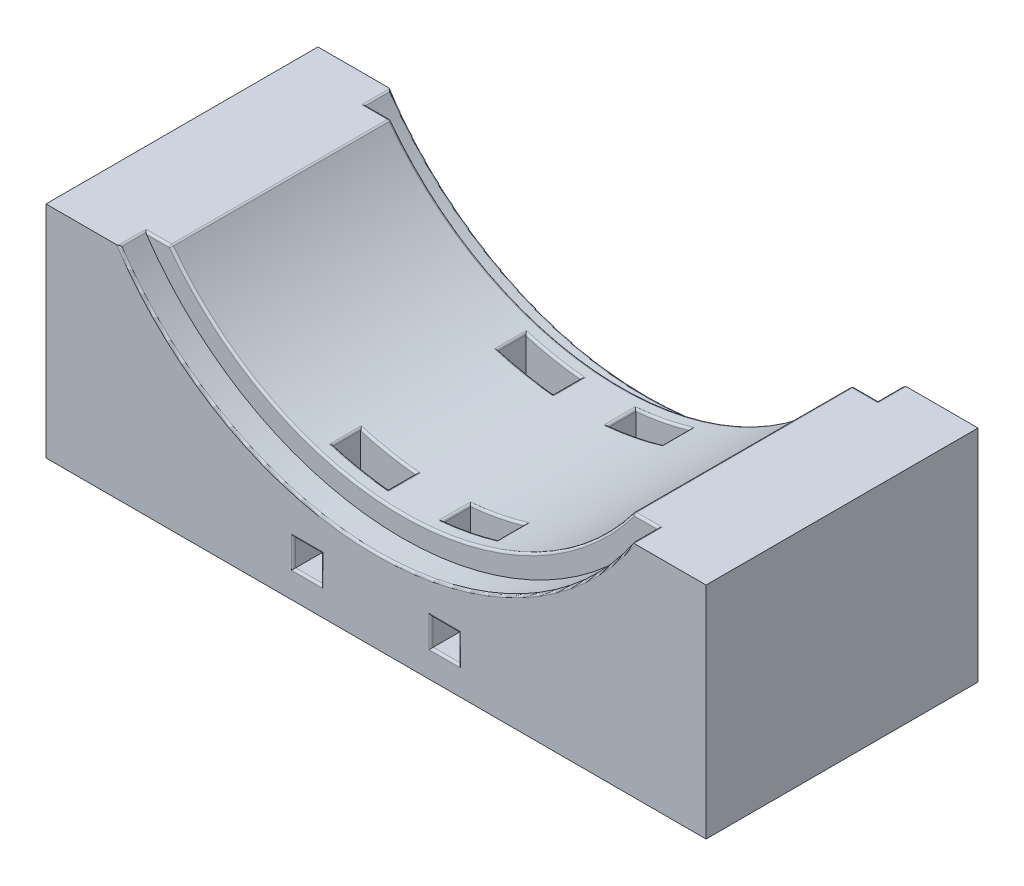
SolidWorks part; units mm, degrees
material "ABS"
ref_plane "Front Plane" through (0, 0, 0) normal (0, 0, 1) x (1, 0, 0)
ref_plane "Top Plane" through (0, 0, 0) normal (0, 1, 0) x (1, 0, 0)
ref_plane "Right Plane" through (0, 0, 0) normal (1, 0, 0) x (0, 0, -1)
sketch "Sketch1" plane through (0, 0, 0) normal (0, 0, 1) x (1, 0, 0)
  line L0 (0, 0) -> (-33941.0899, 0) construction
  line L1 (0, 0) -> (0, 33941.0899) construction
  line L3 (-76.2, 0) -> (76.2, 0)
  line L4 (-76.2, 0) -> (-76.2, 50.8)
  line L5 (-76.2, 50.8) -> (76.2, 50.8)
  line L6 (76.2, 0) -> (76.2, 50.8)
  circle A0 centre (0, 90.4875) radius 71.374
  dimension "D2" = 142.748
  dimension "D3" = 50.8
  dimension "D1" = 90.4875
  dimension "D4" = 152.4
extrude "Boss-Extrude1" add sketch "Sketch1" along normal blind 5.9944 contours A0 L5 L4 L3 L6 region at (0, 18.9439, 0)
sketch "Sketch2" plane through (0, 0, 5.9944) normal (0, 0, 1) x (1, 0, 0)
  line L0 (0, 0) -> (0, 50000) construction
  line L1 (0, 0) -> (-50000, 0) construction
  line L2 (-76.2, 0) -> (76.2, 0) construction
  line L4 (-76.2, 50.8) -> (76.2, 50.8)
  line L5 (-76.2, 50.8) -> (-76.2, 0)
  line L6 (-76.2, 0) -> (76.2, 0)
  line L7 (76.2, 50.8) -> (76.2, 0)
  circle A0 centre (0, 90.4875) radius 66.548
  point P7 (0, 0)
  arc M2 (59.3224, 50.8) -> (-59.3224, 50.8) centre (0, 90.4875) cw
  line M3 (-59.3224, 50.8) -> (-76.2, 50.8)
  line M4 (-76.2, 50.8) -> (-76.2, 0)
  line M5 (-76.2, 0) -> (76.2, 0)
  line M6 (76.2, 0) -> (76.2, 50.8)
  line M7 (76.2, 50.8) -> (59.3224, 50.8)
  dimension "D1" = 133.096
  dimension "D2" = 90.4875
extrude "Boss-Extrude2" add sketch "Sketch2" along normal blind 50.8 contours A0 L4 M2 | M7 M2 M3 M4 M5 M6 region at (0, 18.9439, 5.9944) region at (-56.3705, 49.572, 5.9944)
sketch "Sketch3" plane through (0, 0, 56.7944) normal (0, 0, 1) x (1, 0, 0)
  line L0 (0, 0) -> (0, 50000) construction
  line L1 (0, 0) -> (-47845.2173, 0) construction
  line L4 (-76.2, 50.8) -> (76.2, 50.8)
  line L5 (-76.2, 50.8) -> (-76.2, 0)
  line L6 (-76.2, 0) -> (76.2, 0)
  line L7 (76.2, 50.8) -> (76.2, 0)
  circle A0 centre (0, 90.4875) radius 71.374
  line M4 (-76.2, 50.8) -> (-76.2, 0)
  line M5 (-76.2, 0) -> (76.2, 0)
  line M6 (76.2, 0) -> (76.2, 50.8)
  line M7 (76.2, 50.8) -> (53.4185, 50.8)
  dimension "D1" = 142.748
  dimension "D2" = 90.4875
extrude "Boss-Extrude3" add sketch "Sketch3" along normal blind 5.9944 contours A0 L4 M4 M5 M6 M7 region at (0, 18.9439, 56.7944)
fillet "Fillet1" radius 0.508 14 edges at (0, 19.1135, 62.7888) (0, 23.9395, 56.7944) (0, 19.1135, 0) (0, 23.9395, 5.9944) (-53.4185, 50.8, 31.3944) (53.4185, 50.8, 31.3944)
ref_plane "Plane1" through (0, 23.9395, 0) normal (0, 1, 0) x (1, 0, 0)
sketch "Sketch4" plane through (0, 23.9395, 0) normal (0, 1, 0) x (1, 0, 0)
  line L0 (0, 0) -> (0, -50000) construction
  line L1 (-38.6675, -50.4444) -> (49961.3325, -50.4444) construction
  line L2 (-58.9794, -56.7944) -> (58.9794, -56.7944) construction
  line L3 (-19.05, -47.2694) -> (-19.05, -53.6194)
  line L4 (6.35, -47.2694) -> (19.05, -47.2694)
  line L5 (6.35, -47.2694) -> (6.35, -53.6194)
  line L6 (6.35, -53.6194) -> (19.05, -53.6194)
  line L7 (19.05, -47.2694) -> (19.05, -53.6194)
  line L8 (-6.35, -53.6194) -> (-19.05, -53.6194)
  line L9 (-6.35, -47.2694) -> (-6.35, -53.6194)
  line L10 (-6.35, -47.2694) -> (-19.05, -47.2694)
  line L11 (-76.2, -31.3944) -> (76.2, -31.3944) construction
  line L12 (-76.2, -62.7888) -> (-76.2, 0) construction
  line L13 (76.2, -62.7888) -> (76.2, 0) construction
  line L14 (19.05, -15.5194) -> (19.05, -9.1694)
  line L15 (6.35, -9.1694) -> (19.05, -9.1694)
  line L16 (6.35, -15.5194) -> (6.35, -9.1694)
  line L17 (6.35, -15.5194) -> (19.05, -15.5194)
  line L18 (-6.35, -15.5194) -> (-6.35, -9.1694)
  line L19 (-19.05, -15.5194) -> (-19.05, -9.1694)
  line L20 (-6.35, -9.1694) -> (-19.05, -9.1694)
  line L21 (-6.35, -15.5194) -> (-19.05, -15.5194)
  dimension "D1" = 6.35
  dimension "D2" = 6.35
  dimension "D3" = 6.35
  dimension "D4" = 12.7
extrude "Cut-Extrude1" cut sketch "Sketch4" against normal blind 6.35 and the other way up to next
sketch "Sketch5" plane through (0, 0, 62.7888) normal (0, 0, 1) x (1, 0, 0)
  line L0 (0, 0) -> (0, 50000) construction
  line L1 (-19.05, 12.7) -> (-19.05, 6.35)
  line L2 (12.7, 12.7) -> (19.05, 12.7)
  line L3 (12.7, 12.7) -> (12.7, 6.35)
  line L4 (12.7, 6.35) -> (19.05, 6.35)
  line L5 (19.05, 12.7) -> (19.05, 6.35)
  line L6 (-12.7, 6.35) -> (-19.05, 6.35)
  line L7 (-12.7, 12.7) -> (-12.7, 6.35)
  line L8 (-12.7, 12.7) -> (-19.05, 12.7)
  line L9 (-76.2, 0) -> (76.2, 0) construction
  dimension "D1" = 6.35
  dimension "D2" = 12.7
  dimension "D3" = 6.35
extrude "Cut-Extrude2" cut sketch "Sketch5" against normal blind 12.7
fillet "Fillet2" radius 0.508 24 edges at (-15.875, 6.35, 62.7888) (-12.7, 9.525, 62.7888) (-15.875, 12.7, 62.7888) (-19.05, 9.525, 62.7888) (19.05, 9.525, 62.7888) (15.875, 6.35, 62.7888) (12.7, 9.525, 62.7888) (15.875, 12.7, 62.7888) (19.05, 26.7244, 12.3444) (12.7605, 25.1744, 15.5194) (6.35, 24.2432, 12.3444) (12.7605, 25.1744, 9.1694) (-6.35, 24.2432, 12.3444) (-12.7605, 25.1744, 15.5194) (-12.7605, 25.1744, 9.1694) (-19.05, 26.7244, 12.3444) (19.05, 26.7244, 50.4444) (12.7605, 25.1744, 53.6194) (6.35, 24.2432, 50.4444) (12.7605, 25.1744, 47.2694) (-6.35, 24.2432, 50.4444) (-12.7605, 25.1744, 53.6194) (-19.05, 26.7244, 50.4444) (-12.7605, 25.1744, 47.2694)
